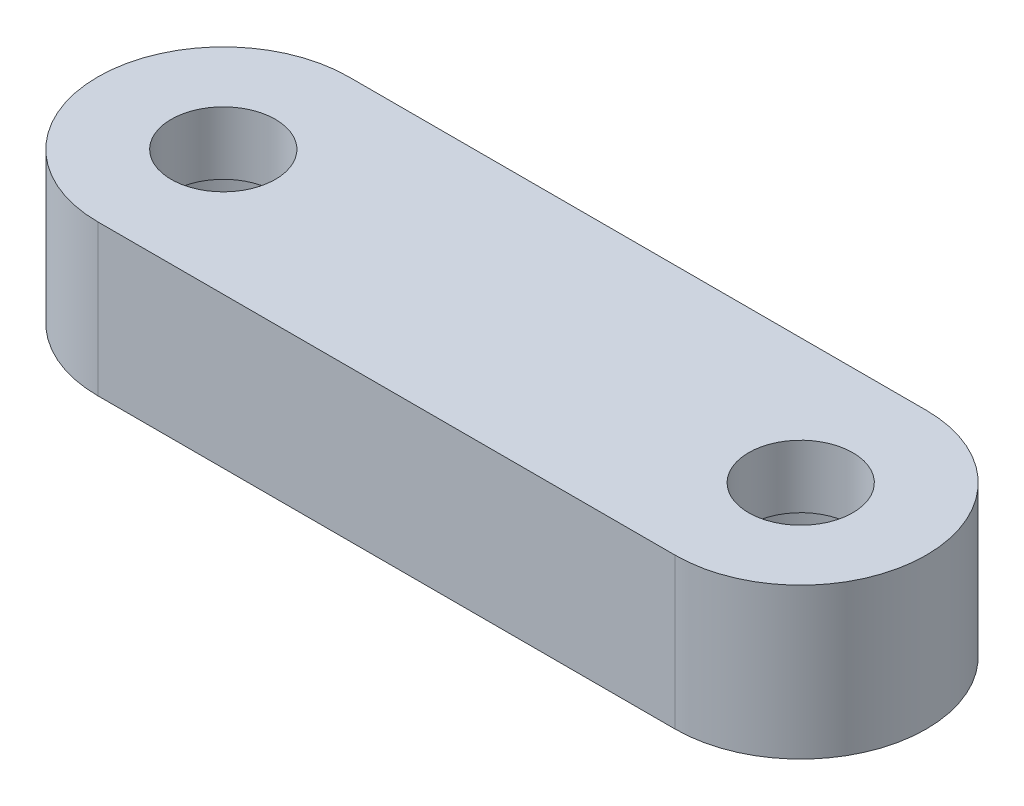
SolidWorks part; units mm, degrees
ref_plane "Front Plane" through (0, 0, 0) normal (0, 0, 1) x (1, 0, 0)
ref_plane "Top Plane" through (0, 0, 0) normal (0, 1, 0) x (1, 0, 0)
ref_plane "Right Plane" through (0, 0, 0) normal (1, 0, 0) x (0, 0, -1)
sketch "Sketch2" plane through (0, 0, 0) normal (0, 1, 0) x (1, 0, 0)
  line L0 (0, 0) -> (23, 0) construction
  line L1 (0, 5) -> (23, 5)
  line L2 (0, -5) -> (23, -5)
  arc A0 (0, 5) -> (0, -5) centre (0, 0) ccw
  arc A1 (23, -5) -> (23, 5) centre (23, 0) ccw
  point P3 (11.5, 0)
  point P8 (0, 0)
  point P9 (0, 0)
  point P10 (23.6856, -1.0908)
  dimension "D1" = 23
  dimension "D2" = 10
extrude "Boss-Extrude1" add sketch "Sketch2" along normal blind 6
sketch "Sketch3" plane through (0, 0, 0) normal (0, 0, 1) x (1, 0, 0)
  line L0 (0, 0) -> (0, 11.9265) construction
  line L1 (0, 0) -> (-3.75, 0)
  line L2 (-5, 0) -> (0, 0) construction
  line L3 (-3.75, 0) -> (-3.75, 3.5)
  line L4 (-3.75, 3.5) -> (-2.075, 3.5)
  line L5 (-2.075, 3.5) -> (-2.075, 6)
  line L6 (0, 6) -> (-5, 6) construction
  line L7 (-2.075, 6) -> (0, 6)
  line L8 (0, 0) -> (0, 6)
  point P3 (-3.75, 1.75)
  dimension "D1" = 4.15
  dimension "D2" = 7.5
  dimension "D3" = 3.5
revolve "Cut-Revolve1" cut sketch "Sketch3" angle 360 about L8
sketch "Sketch4" plane through (0, 0, 0) normal (0, 0, 1) x (1, 0, 0)
  line L0 (23, 0) -> (23, 11.7791) construction
  line L1 (23, 0) -> (19.25, 0)
  line L2 (0, 0) -> (23, 0) construction
  line L3 (19.25, 0) -> (19.25, 3.5)
  line L4 (19.25, 3.5) -> (20.925, 3.5)
  line L5 (20.925, 3.5) -> (20.925, 6)
  line L6 (0, 6) -> (23, 6) construction
  line L7 (20.925, 6) -> (23, 6)
  line L8 (23, 0) -> (23, 6)
  dimension "D1" = 4.15
  dimension "D2" = 7.5
  dimension "D3" = 3.5
revolve "Cut-Revolve2" cut sketch "Sketch4" angle 360 about L8
